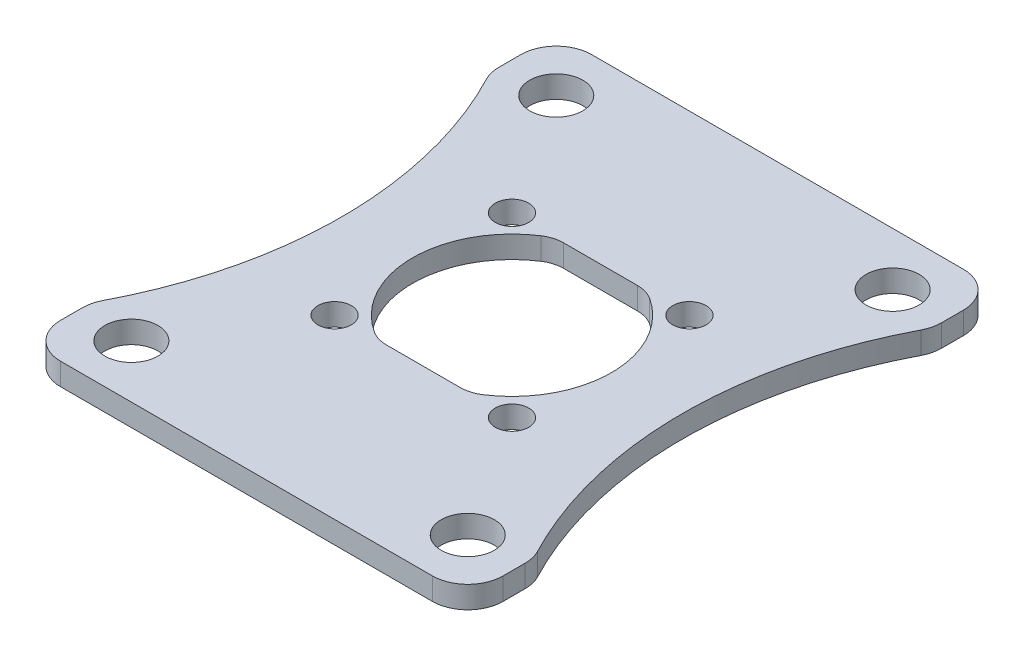
SolidWorks part; units mm, degrees
material "Alum Plate"
ref_plane "Front Plane" through (0, 0, 0) normal (0, 0, 1) x (1, 0, 0)
ref_plane "Top Plane" through (0, 0, 0) normal (0, 1, 0) x (1, 0, 0)
ref_plane "Right Plane" through (0, 0, 0) normal (1, 0, 0) x (0, 0, -1)
sketch "Sketch1" plane through (0, 0, 0) normal (0, 1, 0) x (1, 0, 0)
  line L0 (-6.364, 6.364) -> (6.364, -6.364) construction
  line L1 (-15.875, -19.05) -> (15.875, -19.05)
  line L2 (-15.875, -19.05) -> (-15.875, 19.05)
  line L3 (-15.875, 19.05) -> (15.875, 19.05)
  line L4 (15.875, -19.05) -> (15.875, 19.05)
  line L5 (-15.875, -19.05) -> (15.875, 19.05) construction
  line L6 (-15.875, 19.05) -> (15.875, -19.05) construction
  line L7 (-6.364, -6.364) -> (6.364, 6.364) construction
  line L8 (-6.364, 6.364) -> (-6.364, 19.05) construction
  line L9 (6.364, 6.364) -> (6.364, 19.05) construction
  line L10 (-15.875, 15.24) -> (-12.065, 15.24) construction
  line L11 (-12.065, 15.24) -> (-12.065, 19.05) construction
  line L12 (12.065, 19.05) -> (12.065, 15.24) construction
  line L13 (12.065, 15.24) -> (15.875, 15.24) construction
  line L14 (-12.065, 15.24) -> (0, 0) construction
  line L15 (12.065, -15.24) -> (12.065, -19.05) construction
  line L16 (12.065, -15.24) -> (15.875, -15.24) construction
  line L17 (-12.065, -19.05) -> (-12.065, -15.24) construction
  line L18 (-12.065, -15.24) -> (-15.875, -15.24) construction
  line L19 (-12.065, -15.24) -> (12.065, -15.24) construction
  circle A0 centre (0, 0) radius 7.1374
  circle A1 centre (-6.364, -6.364) radius 1.2
  circle A2 centre (-6.364, 6.364) radius 1.2
  circle A3 centre (6.364, 6.364) radius 1.2
  circle A4 centre (6.364, -6.364) radius 1.2
  circle A5 centre (-12.065, -15.24) radius 1.905
  circle A6 centre (-12.065, 15.24) radius 1.905
  circle A7 centre (12.065, 15.24) radius 1.905
  circle A8 centre (12.065, -15.24) radius 1.905
  circle A9 centre (0, 0) radius 10.9982 construction
  point P0 (0, 0)
  point P18 (0, 0)
  point P19 (0, 0)
  dimension "D1" = 14.2748
  dimension "D2" = 2.4
  dimension "D3" = 9
  dimension "D4" = 3.81
  dimension "D8" = 21.9964
  dimension "D5" = 38.1
  dimension "D6" = 31.75
  dimension "D7" = 3.81
extrude "Boss-Extrude1" add sketch "Sketch1" along normal blind 1.5875
sketch "Sketch3" plane through (0, 1.5875, 0) normal (0, 1, 0) x (1, 0, 0)
  line L0 (-3.2588, 6.35) -> (3.2588, 6.35)
  line L2 (3.2588, -6.35) -> (-3.2588, -6.35)
  arc A0 (-3.2588, -6.35) -> (3.2588, -6.35) centre (0, 0) ccw
  circle A1 centre (0, 0) radius 7.1374 construction
  arc A2 (3.2588, 6.35) -> (-3.2588, 6.35) centre (0, 0) ccw
  dimension "D1" = 12.7
extrude "Boss-Extrude3" add sketch "Sketch3" against normal through all
sketch "Sketch4" plane through (0, 0, 0) normal (0, -1, 0) x (1, 0, 0)
  line L0 (-41.9862, 0) -> (0, 0) construction
  line L1 (0, 0) -> (41.9862, 0) construction
  line L2 (-15.875, -19.05) -> (-15.875, 19.05) construction
  line L3 (15.875, 19.05) -> (15.875, -19.05) construction
  line L4 (-12.2174, 0) -> (-7.1374, 0) construction
  line L5 (-15.875, 14.2964) -> (-15.875, -14.2964)
  line L6 (15.875, -14.2964) -> (15.875, 14.2964)
  line L7 (-15.46, 13.5108) -> (-12.065, 15.24) construction
  arc A0 (-15.875, 14.2964) -> (-15.875, -14.2964) centre (-41.9862, 0) cw
  arc A1 (15.875, 14.2964) -> (15.875, -14.2964) centre (41.9862, 0) ccw
  arc A2 (-3.2588, 6.35) -> (-3.2588, -6.35) centre (0, 0) ccw construction
  dimension "D1" = 3.81
  dimension "D2" = 5.08
extrude "Cut-Extrude1" cut sketch "Sketch4" against normal through all
fillet "Fillet3" radius 2.54 8 edges at (-15.875, 0.7937, -14.2964) (-15.875, 0.7937, -19.05) (15.875, 0.7937, -19.05) (15.875, 0.7937, -14.2964) (15.875, 0.7937, 14.2964) (15.875, 0.7937, 19.05) (-15.875, 0.7937, 19.05) (-15.875, 0.7937, 14.2964)
fillet "Fillet2" radius 2.286 4 edges at (-3.2588, 0.7937, -6.35) (3.2588, 0.7937, -6.35) (-3.2588, 0.7937, 6.35) (3.2588, 0.7937, 6.35)
